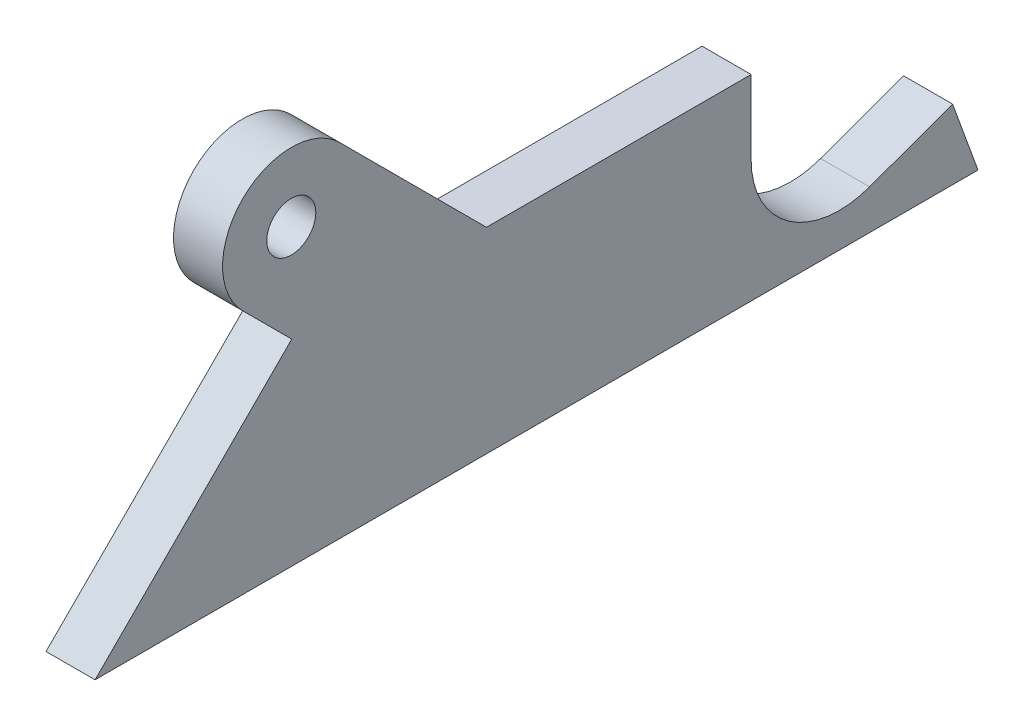
SolidWorks part; units mm, degrees
ref_plane "Front Plane" through (0, 0, 0) normal (0, 0, 1) x (1, 0, 0)
ref_plane "Top Plane" through (0, 0, 0) normal (0, 1, 0) x (1, 0, 0)
ref_plane "Right Plane" through (0, 0, 0) normal (1, 0, 0) x (0, 0, -1)
sketch "Sketch1" plane through (0, 0, 0) normal (1, 0, 0) x (0, 0, -1)
  line L0 (114.3, 0) -> (-114.3, 0)
  line L1 (-114.3, 0) -> (-63.3724, 50.9276)
  line L2 (-63.3724, 50.9276) -> (-76.0724, 63.6276)
  line L3 (-50.9276, 88.7724) -> (-12.9553, 50.8)
  line L6 (114.3, 0) -> (95.8103, 50.8)
  line L8 (-12.9553, 50.8) -> (95.8103, 50.8)
  line L13 (86.2354, 10.2686) -> (107.7168, 18.0872)
  line L14 (55.5568, 31.75) -> (55.5568, 50.8)
  arc A0 (-76.0724, 63.6276) -> (-50.9276, 88.7724) centre (-63.5, 76.2) cw
  circle A1 centre (-63.5, 76.2) radius 6.35
  circle A2 centre (78.4168, 31.75) radius 22.86
  point P4 (0, 0)
  dimension "D2" = 76.2
  dimension "D3" = 17.78
  dimension "D6" = 12.7
  dimension "D7" = 45.72
  dimension "D1" = 45
  dimension "D4" = 50.8
  dimension "D5" = 228.6
  dimension "D8" = 70
  dimension "D9" = 50.8
  dimension "D10" = 31.75
extrude "Boss-Extrude1" add sketch "Sketch1" along normal blind 12.7 contours A0 L2 L1 L0 L3 A1 region at (0, 30.2039, 15.6129)
